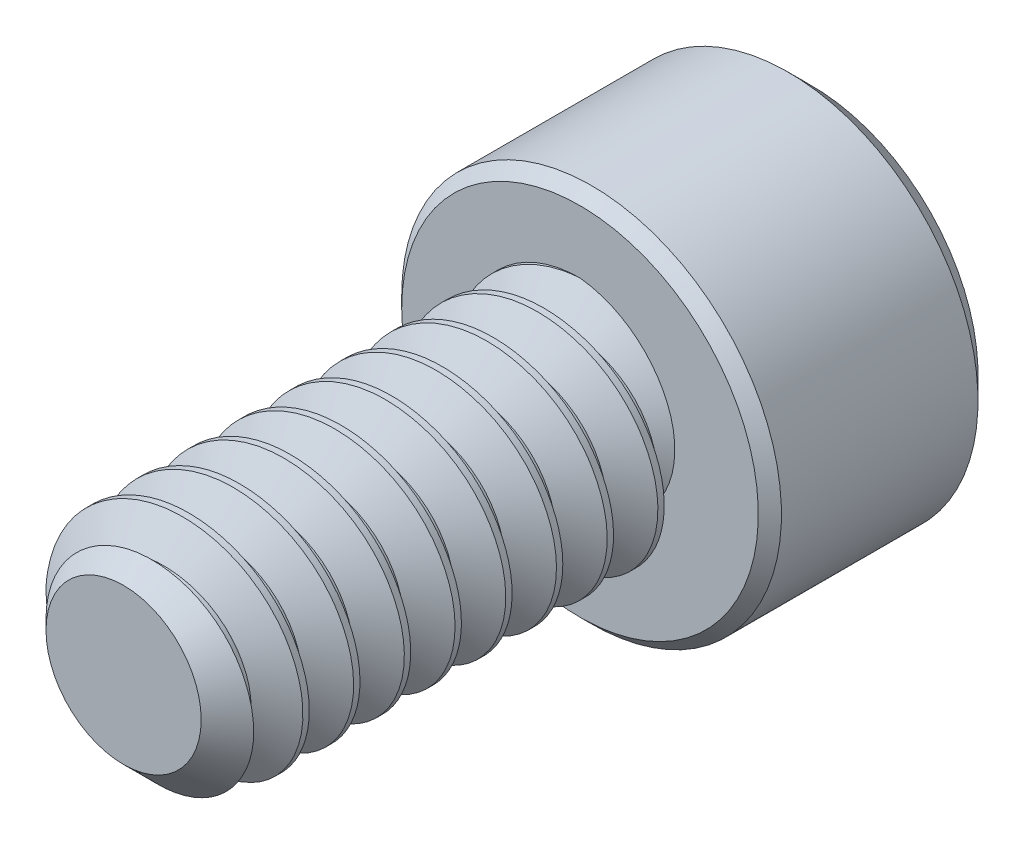
SolidWorks part; units mm, degrees
ref_plane "Front Plane" through (0, 0, 0) normal (0, 0, 1) x (1, 0, 0)
ref_plane "Top Plane" through (0, 0, 0) normal (0, 1, 0) x (1, 0, 0)
ref_plane "Right Plane" through (0, 0, 0) normal (1, 0, 0) x (0, 0, -1)
sketch "Sketch1" plane through (0, 0, 0) normal (0, 0, 1) x (1, 0, 0)
  line L0 (0, 2.413) -> (0, -2.413) construction
  circle A0 centre (0, 0) radius 2.413
  dimension "OD" = 4.826
extrude "Extrude1" add sketch "Sketch1" against normal blind 9.525
sketch "Sketch2" plane through (0, 0, 0) normal (0, 0, 1) x (1, 0, 0)
  circle A0 centre (0, 0) radius 2.413 construction
  circle A1 centre (0, 0) radius 2.413
curve "Helix/Spiral1" pitch 1.0583 height 10.5833 turns 10 parameters "pitch"=1.0583
chamfer "Chamfer3" distance 0.7937 angle 45 1 edges at (2.413, 0, 0)
sketch "Sketch3" plane through (0, 0, 0) normal (1, 0, 0) x (0, 0, -1)
  line L0 (-0.926, 2.413) -> (-0.5292, 1.7256)
  line L1 (-0.5292, 1.7256) -> (-0.3969, 1.7256)
  line L2 (-0.3969, 1.7256) -> (0, 2.413)
  line L3 (-0.926, 2.413) -> (0, 2.413)
  line L4 (-0.463, 2.413) -> (-0.463, 1.7256) construction
  line L5 (-0.7276, 2.0693) -> (-0.1984, 2.0693) construction
  line L6 (0, 2.413) -> (0, -2.413) construction
  dimension "D1" = 0.1323
  dimension "D2" = 0.5292
  dimension "D3" = 60
sweep "Cut-Sweep1" cut profiles "Sketch3" path "Helix/Spiral1"
sketch "Sketch6" plane through (0, 0, -9.525) normal (0, 0, -1) x (-1, 0, 0)
  circle A0 centre (0, 0) radius 3.9624
  dimension "head dia" = 7.9248
extrude "Extrude2" add sketch "Sketch6" along normal blind 4.826
sketch "Sketch7" plane through (0, 0, -14.351) normal (0, 0, -1) x (-1, 0, 0)
  line L1 (0, 2.2914) -> (-1.9844, 1.1457)
  line L2 (-1.9844, 1.1457) -> (-1.9844, -1.1457)
  line L3 (-1.9844, -1.1457) -> (0, -2.2914)
  line L4 (0, -2.2914) -> (1.9844, -1.1457)
  line L5 (1.9844, -1.1457) -> (1.9844, 1.1457)
  line L6 (1.9844, 1.1457) -> (0, 2.2914)
  circle A0 centre (0, 0) radius 1.9844 construction
  dimension "hex dia" = 3.9688
extrude "Cut-Extrude1" cut sketch "Sketch7" against normal blind 2.9766
sketch "Sketch8" plane through (0, 0, -14.351) normal (0, 0, -1) x (-1, 0, 0)
  circle A0 centre (0, 0) radius 2.2914
extrude "Cut-Extrude2" cut sketch "Sketch8" against normal blind 0.4826 draft 45
chamfer "Chamfer1" distance 0.4826 angle 45 1 edges at (-3.9624, 0, -14.351)
chamfer "Chamfer2" distance 0.2413 angle 45 1 edges at (-3.9624, 0, -9.525)
sketch "Sketch9" plane through (0, 0, 0) normal (1, 0, 0) x (0, 0, -1)
  line L0 (0, 2.413) -> (0, -2.413) construction
  line L1 (5.8208, 2.413) -> (5.8208, -2.413) construction
  line L2 (9.525, 3.9624) -> (9.525, -3.9624) construction
  line L3 (14.351, 3.9624) -> (14.351, -3.9624) construction
  line L4 (14.351, 0) -> (0, 0) construction
  dimension "D1" = 5.8208
  dimension "D2" = 4.826
  dimension "D3" = 7.9248
  dimension "D4" = 9.525
equation "\"D3@Helix/Spiral1\" = \"screw length@Extrude1\"+\"pitch@Helix/Spiral1\""
equation "\"D1@Sketch3\" = \"pitch@Helix/Spiral1\"*.125"
equation "\"D2@Sketch3\" = \"pitch@Helix/Spiral1\"*.5"
equation "\"D1@Cut-Extrude1\" = \"hex dia@Sketch7\"*.75"
equation "\"D1@Chamfer1\" = \"head depth@Extrude2\"/10"
equation "\"D1@Sketch9\" = \"pitch@Helix/Spiral1\"*5.5"
equation "\"D1@Chamfer2\" = \"D1@Chamfer1\"/2"
equation "\"D1@Cut-Extrude2\" = \"D1@Chamfer2\"*2"
equation "\"D1@Chamfer3\" = \"pitch@Helix/Spiral1\"*.750"
equation "\"D2@Sketch9\" = \"head depth@Extrude2\""
equation "\"D3@Sketch9\" = \"head dia@Sketch6\""
equation "\"D4@Sketch9\" = \"screw length@Extrude1\""
